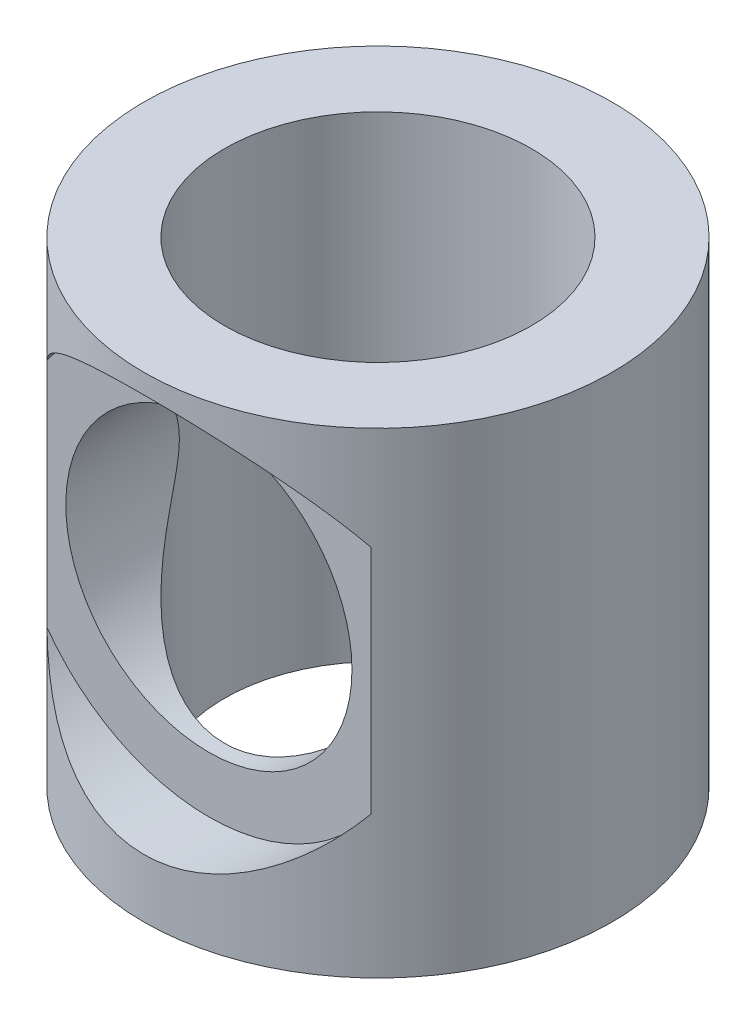
SolidWorks part; units mm, degrees
material "PTFE (general)"
ref_plane "Front Plane" through (0, 0, 0) normal (0, 0, 1) x (1, 0, 0)
ref_plane "Top Plane" through (0, 0, 0) normal (0, 1, 0) x (1, 0, 0)
ref_plane "Right Plane" through (0, 0, 0) normal (1, 0, 0) x (0, 0, -1)
sketch "Sketch1" plane through (0, 0, 0) normal (0, 1, 0) x (1, 0, 0)
  circle A0 centre (0, 0) radius 9
  circle A1 centre (0, 0) radius 5.9
  dimension "D1" = 18
  dimension "D2" = 11.8
extrude "Boss-Extrude1" add sketch "Sketch1" against normal blind 18.3
sketch "Sketch3" plane through (0, 0, 0) normal (0, 0, 1) x (1, 0, 0)
  line L1 (5.9, 0) -> (-5.9, 0) construction
  circle A0 centre (0, -8.4) radius 7.65
  dimension "D1" = 15.3
  dimension "D2" = 8.4
extrude "Cut-Extrude5" cut sketch "Sketch3" along normal through all from offset 6.5
sketch "Sketch6" plane through (0, 0, 6.5) normal (0, 0, 1) x (1, 0, 0)
  line L0 (-6.2249, -18.3) -> (6.2249, -18.3) construction
  circle A0 centre (0, -8.4) radius 5.5
  dimension "D1" = 11
  dimension "D2" = 9.9
  dimension "D3" = 0
extrude "Cut-Extrude6" cut sketch "Sketch6" against normal blind 7 and the other way through all
